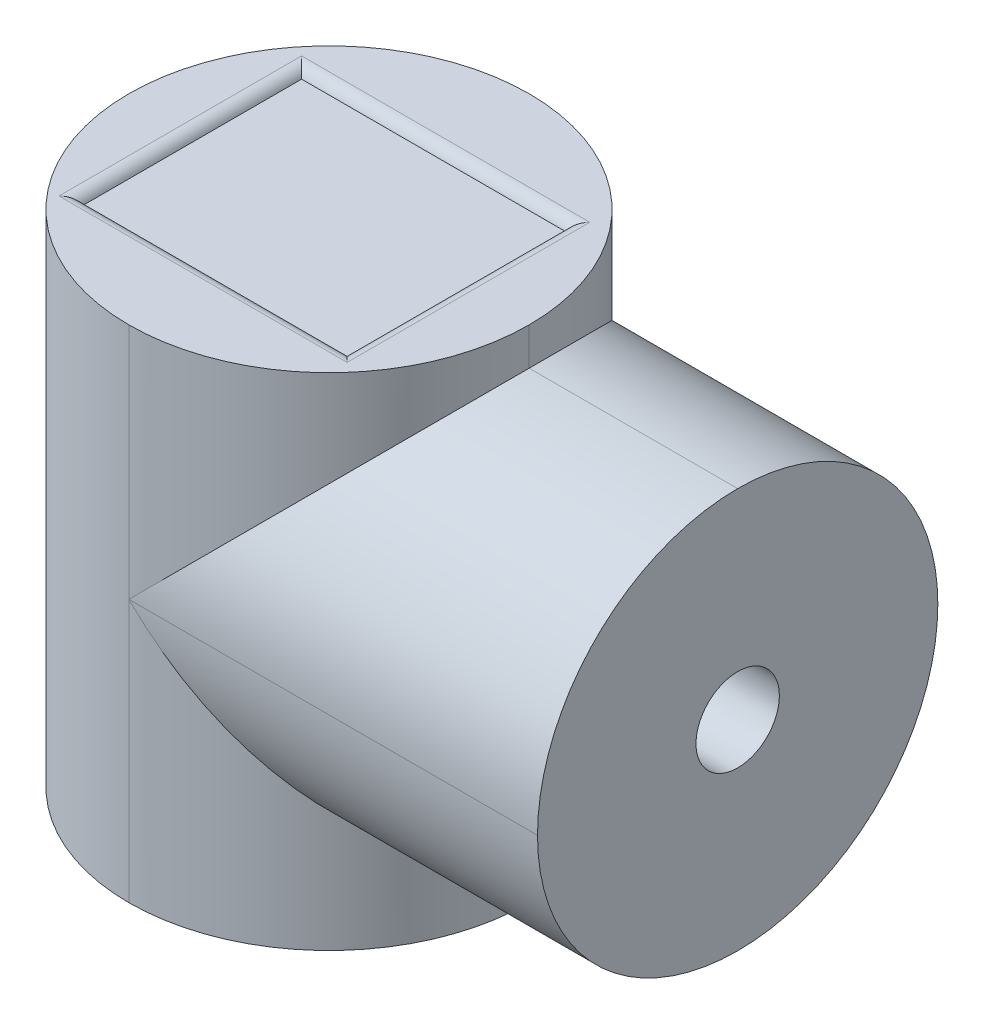
SolidWorks part; units mm, degrees
ref_plane "Front Plane" through (0, 0, 0) normal (0, 0, 1) x (1, 0, 0)
ref_plane "Top Plane" through (0, 0, 0) normal (0, 1, 0) x (1, 0, 0)
ref_plane "Right Plane" through (0, 0, 0) normal (1, 0, 0) x (0, 0, -1)
sketch "Sketch1" plane through (0, 0, 0) normal (0, 1, 0) x (1, 0, 0)
  line L1 (0, 0) -> (48, 0)
  line L2 (0, 0) -> (0, 48)
  line L3 (0, 48) -> (48, 48)
  line L4 (48, 0) -> (48, 48)
  dimension "D1" = 48
  dimension "D2" = 48
extrude "Boss-Extrude1" add sketch "Sketch1" along normal blind 60
sketch "Sketch2" plane through (48, 0, 0) normal (1, 0, 0) x (0, 0, -1)
  line L0 (0, 60) -> (0, 0) construction
  line L1 (0, 55.5) -> (48, 55.5)
  line L2 (0, 55.5) -> (0, 7.5)
  line L3 (0, 7.5) -> (48, 7.5)
  line L4 (48, 55.5) -> (48, 7.5)
  line L5 (48, 60) -> (48, 0) construction
  line L6 (0, 60) -> (48, 60) construction
  dimension "D1" = 48
  dimension "D2" = 4.5
extrude "Boss-Extrude2" add sketch "Sketch2" along normal blind 25
fillet "Fillet1" radius 24 10 edges at (0, 30, 0) (0, 30, -48) (48, 57.75, -48) (48, 57.75, 0) (48, 3.75, -48) (48, 3.75, 0) (60.5, 7.5, 0) (60.5, 55.5, 0) (60.5, 7.5, -48) (60.5, 55.5, -48)
sketch "Sketch3" plane through (0, 0, 0) normal (0, -1, 0) x (-1, 0, 0)
  circle A0 centre (-24, 24) radius 5
  dimension "D1" = 10
extrude "Boss-Extrude3" add sketch "Sketch3" along normal blind 10
sketch "Sketch4" plane through (73, 0, 0) normal (1, 0, 0) x (0, 0, -1)
  circle A0 centre (24, 31.5) radius 5
  dimension "D1" = 10
extrude "Cut-Extrude1" cut sketch "Sketch4" against normal blind 15
sketch "Sketch5" plane through (0, 60, 0) normal (0, 1, 0) x (1, 0, 0)
  line L1 (7.8412, 36.8703) -> (39.5679, 36.8703)
  line L2 (7.8412, 36.8703) -> (7.8412, 10.6059)
  line L3 (7.8412, 10.6059) -> (39.5679, 10.6059)
  line L4 (39.5679, 36.8703) -> (39.5679, 10.6059)
extrude "Cut-Extrude2" cut sketch "Sketch5" against normal blind 2
sketch "Sketch8" plane through (0, 58, 0) normal (0, 1, 0) x (1, 0, 0)
  line L1 (7.8412, 36.8703) -> (39.5679, 36.8703)
  line L2 (7.8412, 36.8703) -> (7.8412, 10.6059)
  line L3 (7.8412, 10.6059) -> (39.5679, 10.6059)
  line L4 (39.5679, 36.8703) -> (39.5679, 10.6059)
extrude "Boss-Extrude6" add sketch "Sketch8" along normal blind 1
fillet "Fillet3" radius 1.5 4 edges at (23.7045, 60, -10.6059) (39.5679, 60, -23.7381) (7.8412, 60, -23.7381) (23.7045, 60, -36.8703)
